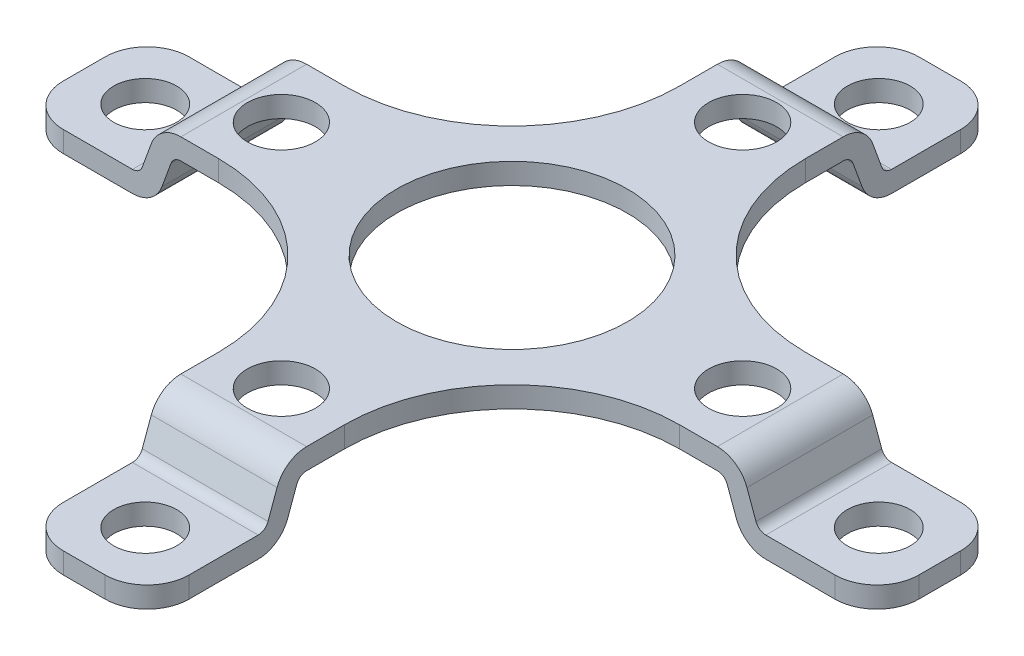
SolidWorks part; units mm, degrees
note: '?' marks a value the reader was unsure of.
material "Plain Carbon Steel"
ref_plane "Front Plane" through (0, 0, 0) normal (0, 0, 1) x (1, 0, 0)
ref_plane "Top Plane" through (0, 0, 0) normal (0, 1, 0) x (1, 0, 0)
ref_plane "Right Plane" through (0, 0, 0) normal (1, 0, 0) x (0, 0, -1)
sketch "Sketch1" plane through (0, 0, 0) normal (0, 0, 1) x (1, 0, 0)
  line L0 (-20.4099, -2.5) -> (-15.1101, -2.5)
  line L1 (-14.1704, -1.842) -> (-13.7395, -0.658)
  line L2 (-12.7998, 0) -> (0, 0)
  arc A0 (-13.7395, -0.658) -> (-12.7998, 0) centre (-12.7998, -1) cw
  arc A1 (-15.1101, -2.5) -> (-14.1704, -1.842) centre (-15.1101, -1.5) ccw
  point P13 (-13.5, 0)
  point P16 (-14.4099, -2.5)
  dimension "D5" = 1
  dimension "D1" = 110
  dimension "D2" = 13.5
  dimension "D3" = 6
  dimension "D4" = 2.5
extrude "Extrude-Thin1" add sketch "Sketch1" along normal mid plane 6 thin thin type mid plane wall 1
fillet "Fillet1" radius 2 2 edges at (-20.4099, -2.5, -3) (-20.4099, -2.5, 3)
mirror "Mirror1" about plane through (0, 0.5, 3) normal (1, 0, 0) of "Fillet1", "Extrude-Thin1"
ref_axis "Axis1" through (0, -3.9913, 0) along (0, 1, 0)?
pattern_circular "CirPattern1" count 2 every 90 about axis through (0, 0, 0) along (0, 1, 0) of bodies 102
sketch "Sketch3" plane through (0, 0.5, 0) normal (0, 1, 0) x (1, 0, 0)
  line L0 (-11.005, 0) -> (11.005, 0) construction
  circle A0 centre (11.005, 0) radius 1.625
  circle A1 centre (0, -11.005) radius 1.625
  circle A2 centre (-11.005, 0) radius 1.625
  circle A3 centre (0, 11.005) radius 1.625
  point P6 (0, 0)
  point P15 (0, 0)
  dimension "D2" = 3.25
  dimension "D1" = 22.01
  dimension "D3" = 4
extrude "Cut-Extrude1" cut sketch "Sketch3" against normal through all both and the other way through all
sketch "Sketch4" plane through (0, -2, 0) normal (0, 1, 0) x (1, 0, 0)
  line L0 (0, 0) -> (-17.5, 0) construction
  circle A0 centre (-17.5, 0) radius 1.5
  circle A1 centre (0, 17.5) radius 1.5
  circle A2 centre (17.5, 0) radius 1.5
  circle A3 centre (0, -17.5) radius 1.5
  point P13 (0, 0)
  dimension "D2" = 3
  dimension "D1" = 17.5
  dimension "D3" = 4
extrude "Cut-Extrude2" cut sketch "Sketch4" against normal through all both and the other way through all
combine bodies "Combine2" bodies to combine 106 107
fillet "Fillet2" radius 8 4 edges at (-3, 0, -3) (3, 0, -3) (-3, 0, 3) (3, 0, 3)
sketch "Sketch5" plane through (0, 0.5, 0) normal (0, 1, 0) x (1, 0, 0)
  circle A0 centre (0, 0) radius 5.5
  dimension "D1" = 11
extrude "Cut-Extrude3" cut sketch "Sketch5" against normal through all both and the other way through all
